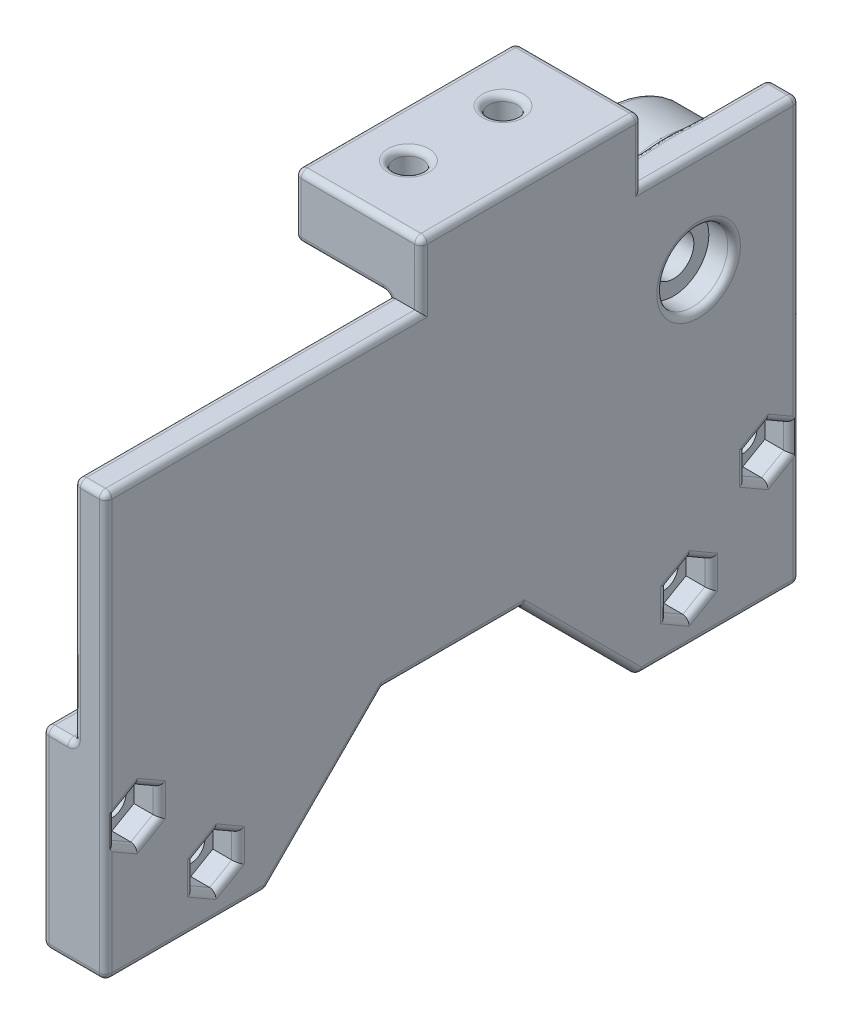
SolidWorks part; units mm, degrees
ref_plane "Front Plane" through (0, 0, 0) normal (0, 0, 1) x (1, 0, 0)
ref_plane "Top Plane" through (0, 0, 0) normal (0, 1, 0) x (1, 0, 0)
ref_plane "Right Plane" through (0, 0, 0) normal (1, 0, 0) x (0, 0, -1)
sketch "Sketch2" plane through (0, 0, 0) normal (1, 0, 0) x (0, 0, -1)
  line L2 (0, 0) -> (0, 67)
  line L4 (110, 0) -> (110, 67)
  line L5 (50, 77) -> (85, 77)
  line L10 (25.5, 0) -> (44, 18.5)
  line L13 (0, 0) -> (25.5, 0)
  line L14 (84.5, 0) -> (110, 0)
  line L16 (0, 67) -> (50, 67)
  line L19 (85, 77) -> (85, 67)
  line L22 (50, 77) -> (50, 67)
  line L25 (44, 18.5) -> (66, 18.5)
  line L26 (66, 18.5) -> (84.5, 0)
  line L27 (85, 67) -> (110, 67)
  circle A0 centre (17.5, 8) radius 2.25
  circle A1 centre (5, 20.5) radius 2.25
  circle A2 centre (92.5, 8) radius 2.25
  circle A3 centre (105, 20.5) radius 2.25
  dimension "D2" = 35
  dimension "D3" = 77
  dimension "D4" = 4.5
  dimension "D5" = 12.5
  dimension "D6" = 25
  dimension "D7" = 12.5
  dimension "D8" = 12.5
  dimension "D9" = 100
  dimension "D10" = 5
  dimension "D11" = 5
  dimension "D12" = 18.5
  dimension "D13" = 8
  dimension "D14" = 8
  dimension "D15" = 10
  dimension "D17" = 45
extrude "Boss-Extrude2" add sketch "Sketch2" along normal blind 5
sketch "Sketch3" plane through (0, 0, 0) normal (-1, 0, 0) x (0, 0, 1)
  line L1 (-85, 77) -> (-50, 77)
  line L2 (-85, 77) -> (-85, 67)
  line L3 (-85, 67) -> (-50, 67)
  line L4 (-50, 77) -> (-50, 67)
  line L5 (-85, 67) -> (-85, 77) construction
  line L6 (-50, 77) -> (-50, 67) construction
  line L7 (-85, 77) -> (-50, 77) construction
  dimension "D1" = 10
extrude "Boss-Extrude6" add sketch "Sketch3" along normal blind 15
sketch "Sketch4" plane through (0, 67, 0) normal (0, -1, 0) x (1, 0, 0)
  line L0 (-15, -85) -> (-15, -50) construction
  line L1 (-7, -60) -> (-7, -50) construction
  line L2 (-15, -50) -> (0, -50) construction
  line L3 (-7, -75) -> (-7, -85) construction
  line L4 (-15, -85) -> (0, -85) construction
  circle A0 centre (-7, -60) radius 2.25
  circle A1 centre (-7, -75) radius 2.25
  dimension "D1" = 8
  dimension "D2" = 4.5
  dimension "D3" = 15
extrude "Cut-Extrude1" cut sketch "Sketch4" against normal blind 10
sketch "Sketch5" plane through (0, 67, 0) normal (0, -1, 0) x (1, 0, 0)
  line L1 (-4.9793, -63.5) -> (-2.9585, -60)
  line L2 (-2.9585, -60) -> (-4.9793, -56.5)
  line L3 (-4.9793, -56.5) -> (-9.0207, -56.5)
  line L4 (-9.0207, -56.5) -> (-11.0415, -60)
  line L5 (-11.0415, -60) -> (-9.0207, -63.5)
  line L6 (-9.0207, -63.5) -> (-4.9793, -63.5)
  line L7 (-11.0415, -75) -> (-9.0207, -78.5)
  line L8 (-9.0207, -78.5) -> (-4.9793, -78.5)
  line L9 (-4.9793, -78.5) -> (-2.9585, -75)
  line L10 (-2.9585, -75) -> (-4.9793, -71.5)
  line L11 (-4.9793, -71.5) -> (-9.0207, -71.5)
  line L12 (-9.0207, -71.5) -> (-11.0415, -75)
  circle A0 centre (-7, -60) radius 3.5 construction
  circle A1 centre (-7, -75) radius 3.5 construction
  dimension "D1" = 7
extrude "Cut-Extrude2" cut sketch "Sketch5" against normal blind 4
sketch "Sketch6" plane through (0, 0, 0) normal (1, 0, 0) x (0, 0, -1)
  line L0 (110, 0) -> (110, 67) construction
  line L1 (110, 67) -> (85, 67) construction
  circle A0 centre (94, 51) radius 15
  dimension "D3" = 30
  dimension "D1" = 16
  dimension "D2" = 16
extrude "Boss-Extrude7" add sketch "Sketch6" against normal blind 10
sketch "Sketch7" plane through (-10, 0, 0) normal (-1, 0, 0) x (0, 0, 1)
  circle A0 centre (-94, 51) radius 3.25
  circle A1 centre (-94, 51) radius 15 construction
  dimension "D1" = 6.5
extrude "Cut-Extrude3" cut sketch "Sketch7" against normal blind 38
sketch "Sketch8" plane through (-10, 0, 0) normal (1, 0, 0) x (0, 0, -1)
  line L1 (94, 44.5048) -> (99.625, 47.7524)
  line L2 (99.625, 47.7524) -> (99.625, 54.2476)
  line L3 (99.625, 54.2476) -> (94, 57.4952)
  line L4 (94, 57.4952) -> (88.375, 54.2476)
  line L5 (88.375, 54.2476) -> (88.375, 47.7524)
  line L6 (88.375, 47.7524) -> (94, 44.5048)
  circle A0 centre (94, 51) radius 5.625 construction
  dimension "D1" = 11.25
extrude "Cut-Extrude5" cut sketch "Sketch8" along normal blind 6
sketch "Sketch9" plane through (5, 0, 0) normal (1, 0, 0) x (0, 0, -1)
  circle A0 centre (94, 51) radius 5.625
  dimension "D1" = 11.25
extrude "Cut-Extrude6" cut sketch "Sketch9" against normal blind 4
sketch "Sketch12" plane through (0, 0, 0) normal (-1, 0, 0) x (0, 0, 1)
  line L0 (-110, 0) -> (-84.5, 0)
  line L1 (-84.5, 0) -> (-77.4289, 7.0711)
  line L2 (-66, 18.5) -> (-84.5, 0) construction
  line L3 (-77.4289, 7.0711) -> (-100.8579, 30.5)
  line L4 (-100.8579, 30.5) -> (-110, 30.5)
  line L5 (-110, 0) -> (-110, 67) construction
  line L6 (-110, 30.5) -> (-110, 0)
  line L7 (-25.5, 0) -> (0, 0)
  line L8 (0, 0) -> (0, 30.5)
  line L9 (0, 67) -> (0, 0) construction
  line L10 (0, 30.5) -> (-9.1421, 30.5)
  line L11 (-9.1421, 30.5) -> (-32.5711, 7.0711)
  line L12 (-25.5, 0) -> (-44, 18.5) construction
  line L13 (-32.5711, 7.0711) -> (-25.5, 0)
  circle A0 centre (-92.5, 8) radius 2.25 construction
  circle A1 centre (-5, 20.5) radius 2.25 construction
  circle A2 centre (-105, 20.5) radius 2.25 construction
  dimension "D1" = 10
  dimension "D2" = 10
  dimension "D3" = 10
  dimension "D4" = 10
extrude "Boss-Extrude8" add sketch "Sketch12" along normal blind 5
sketch "Sketch13" plane through (5, 0, 0) normal (1, 0, 0) x (0, 0, -1)
  circle A0 centre (5, 20.5) radius 2.25
  circle A1 centre (17.5, 8) radius 2.25
  circle A2 centre (105, 20.5) radius 2.25
  circle A3 centre (92.5, 8) radius 2.25
extrude "Cut-Extrude8" cut sketch "Sketch13" against normal blind 10
sketch "Sketch10" plane through (5, 0, 0) normal (1, 0, 0) x (0, 0, -1)
  line L1 (5, 16.4585) -> (8.5, 18.4793)
  line L2 (8.5, 18.4793) -> (8.5, 22.5207)
  line L3 (8.5, 22.5207) -> (5, 24.5415)
  line L4 (5, 24.5415) -> (1.5, 22.5207)
  line L5 (1.5, 22.5207) -> (1.5, 18.4793)
  line L6 (1.5, 18.4793) -> (5, 16.4585)
  line L7 (17.5, 3.9585) -> (21, 5.9793)
  line L8 (21, 5.9793) -> (21, 10.0207)
  line L9 (21, 10.0207) -> (17.5, 12.0415)
  line L10 (17.5, 12.0415) -> (14, 10.0207)
  line L11 (14, 10.0207) -> (14, 5.9793)
  line L12 (14, 5.9793) -> (17.5, 3.9585)
  line L13 (92.5, 3.9585) -> (96, 5.9793)
  line L14 (96, 5.9793) -> (96, 10.0207)
  line L15 (96, 10.0207) -> (92.5, 12.0415)
  line L16 (92.5, 12.0415) -> (89, 10.0207)
  line L17 (89, 10.0207) -> (89, 5.9793)
  line L18 (89, 5.9793) -> (92.5, 3.9585)
  line L19 (105, 16.4585) -> (108.5, 18.4793)
  line L20 (108.5, 18.4793) -> (108.5, 22.5207)
  line L21 (108.5, 22.5207) -> (105, 24.5415)
  line L22 (105, 24.5415) -> (101.5, 22.5207)
  line L23 (101.5, 22.5207) -> (101.5, 18.4793)
  line L24 (101.5, 18.4793) -> (105, 16.4585)
  circle A0 centre (5, 20.5) radius 3.5 construction
  circle A1 centre (17.5, 8) radius 3.5 construction
  circle A2 centre (92.5, 8) radius 3.5 construction
  circle A3 centre (105, 20.5) radius 3.5 construction
  dimension "D1" = 7
extrude "Cut-Extrude7" cut sketch "Sketch10" against normal blind 4
ref_plane "Plane1" through (0, 0, -67.5) normal (0, 0, -1) x (-1, 0, 0)
sketch "Sketch15" plane through (0, 0, -67.5) normal (0, 0, -1) x (-1, 0, 0)
  line L0 (10, 67) -> (0, 67)
  line L1 (0, 67) -> (0, 57)
  line L2 (0, 57) -> (10, 67)
  dimension "D1" = 45
  dimension "D2" = 10
extrude "Boss-Extrude9" add sketch "Sketch15" along normal blind 2 and the other way blind 2
fillet "Fillet1" radius 1 55 edges at (5, 51, -99.625) (5, 17.4689, -106.75) (5, 20.5, -108.5) (5, 23.5311, -106.75) (5, 23.5311, -103.25) (5, 20.5, -101.5) (5, 17.4689, -103.25) (5, 4.9689, -94.25) (5, 8, -96) (5, 11.0311, -94.25) (5, 11.0311, -90.75) (5, 8, -89) (5, 4.9689, -90.75) (5, 4.9689, -19.25) (5, 8, -21) (5, 11.0311, -19.25) (5, 11.0311, -15.75) (5, 8, -14) (5, 4.9689, -15.75) (5, 20.5, -8.5) (5, 23.5311, -6.75) (5, 23.5311, -3.25) (5, 20.5, -1.5) (5, 17.4689, -3.25) (5, 17.4689, -6.75) (-15, 77, -67.5) (-5, 77, -85) (5, 72, -50) (5, 67, -25) (5, 33.5, 0) (5, 0, -12.75) (5, 9.25, -34.75) (5, 18.5, -55) (5, 9.25, -75.25) (5, 0, -97.25) (5, 33.5, -110) (5, 67, -97.5) (5, 72, -85) (5, 77, -67.5) (-5, 77, -50) (-7, 77, -77.25) (-7, 77, -62.25) (0, 30.5, -105.4289) (0, 18.7855, -89.1434) (0, 67, -57.75) (0, 67, -77.25) (-10, 67, -67.5) (-5, 67, -69.5) (0, 62, -69.5) (0, 57, -67.5) (0, 62, -65.5) (-5, 67, -65.5) (0, 30.5, -4.5711) (0, 18.7855, -20.8566) (0, 51, -109)
fillet "Fillet2" radius 1 10 edges at (0, 67, -89.5) (-3, 30.5, -110) (0, 59, -110) (0, 67, -102) (0, 41.25, -110) (-3, 30.5, 0) (-0.2929, 30.7929, 0) (-0.2929, 30.7929, -110) (0, 67, -25) (0, 49.25, 0)
fillet "Fillet3" radius 1 41 edges at (-8, 67, -50) (-15, 67, -67.5) (-8, 67, -85) (-3, 7.0711, -77.4289) (-0.2929, 7.2782, -77.2218) (-3, 7.0711, -32.5711) (-0.2929, 7.2782, -32.7782) (-0.0761, 56.9685, -70.1173) (-0.6173, 57.6173, -69.5761) (-10.0315, 66.9239, -70.1173) (-9.3827, 66.3827, -69.5761) (-0.0761, 56.9685, -64.8827) (-0.6173, 57.6173, -65.4239) (-10.0315, 66.9239, -64.8827) (-9.3827, 66.3827, -65.4239) (-0.2929, 66.7071, -50) (-0.2929, 66.7071, -85) (-10.0311, 67, -73.25) (-10.0311, 67, -76.75) (-7, 67, -78.5) (-3.9689, 67, -76.75) (-3.9689, 67, -73.25) (-7, 67, -71.5) (-7, 67, -63.5) (-3.9689, 67, -61.75) (-3.9689, 67, -58.25) (-7, 67, -56.5) (-10.0311, 67, -58.25) (-10.0311, 67, -61.75) (-10, 55.8714, -91.1875) (-10, 55.8714, -96.8125) (-10, 51, -99.625) (-10, 46.1286, -96.8125) (-10, 46.1286, -91.1875) (-10, 51, -88.375) (-10, 51, -109) (0, 13.1391, -71.3609) (0, 18.5, -55) (0, 13.1391, -38.6391) (-5, 62, -69.5) (-5, 62, -65.5)
fillet "Fillet4" radius 1 18 edges at (-5, 30.5, -104.9289) (-5, 14.75, -110) (-5, 0, -97.25) (-5, 3.182, -81.318) (-5, 19.1391, -89.497) (-5, 20.5, -107.25) (-5, 8, -94.75) (-5, 30.2071, -109.7071) (-5, 7.0711, -32.1569) (-5, 30.2071, -0.2929) (-5, 7.0711, -77.8431) (-5, 30.5, -5.0711) (-5, 19.1391, -20.503) (-5, 3.182, -28.682) (-5, 0, -12.75) (-5, 14.75, 0) (-5, 8, -19.75) (-5, 20.5, -7.25)
fillet "Fillet5" radius 1 30 edges at (4.7071, 66.7071, -109.7071) (0.2929, 66.7071, -109.7071) (4.7071, 0.2929, -109.7071) (-4.7071, 0.2929, -109.7071) (4.7071, 66.7071, -0.2929) (0.2929, 66.7071, -0.2929) (4.7071, 0.2929, -0.2929) (-4.7071, 0.2929, -0.2929) (4.7071, 18.7929, -43.8787) (0.2929, 18.7929, -43.8787) (4.7071, 0.2929, -25.3787) (-4.7071, 0.2929, -25.3787) (4.7071, 18.7929, -66.1213) (0.2929, 18.7929, -66.1213) (4.7071, 0.2929, -84.6213) (-4.7071, 0.2929, -84.6213) (-14.7071, 67.2929, -50.2929) (-14.7071, 76.7071, -50.2929) (-14.7071, 76.7071, -84.7071) (-14.7071, 67.2929, -84.7071) (2.5, 67, -110) (0, 0, -110) (2.5, 67, 0) (0, 0, 0) (2.5, 18.5, -44) (0, 0, -25.5) (2.5, 18.5, -66) (0, 0, -84.5) (-15, 72, -50) (-15, 72, -85)
